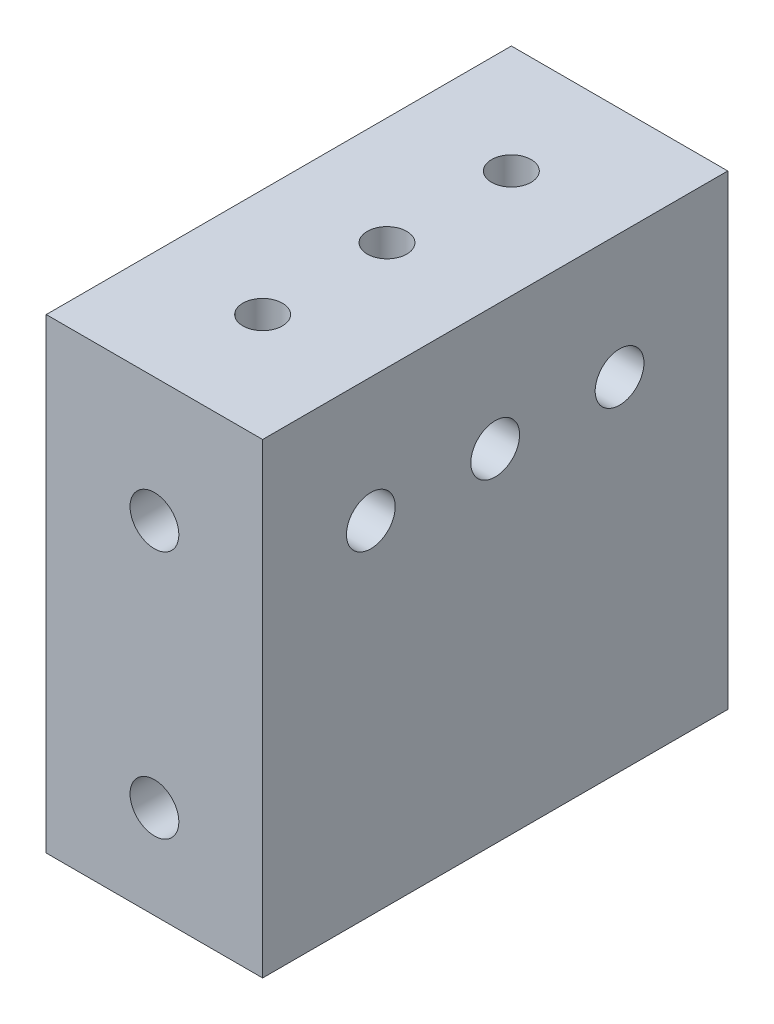
SolidWorks part; units mm, degrees
other "Markup1"
sketch "Sketch3" plane through (12.6365, 38.1, -23.749) normal (0.9027, 0.4189, -0.0984) x (-0.0151, -0.1977, -0.9801)
other "Markup2"
sketch "Sketch4" plane through (12.6365, 38.1, -23.749) normal (0.9027, 0.4189, -0.0984) x (-0.0151, -0.1977, -0.9801)
ref_plane "Front Plane" through (0, 0, 0) normal (0, 0, 1) x (1, 0, 0)
ref_plane "Top Plane" through (0, 0, 0) normal (0, 1, 0) x (1, 0, 0)
ref_plane "Right Plane" through (0, 0, 0) normal (1, 0, 0) x (0, 0, -1)
sketch "Sketch1" plane through (0, 0, 0) normal (0, 1, 0) x (1, 0, 0)
  line L0 (-12.6365, 25.3365) -> (12.6365, 25.3365)
  line L1 (-11.049, -23.749) -> (11.049, -23.749)
  line L2 (-11.049, -23.749) -> (-11.049, 23.749)
  line L3 (-11.049, 23.749) -> (11.049, 23.749)
  line L4 (11.049, -23.749) -> (11.049, 23.749)
  line L5 (-11.049, -23.749) -> (11.049, 23.749) construction
  line L6 (-11.049, 23.749) -> (11.049, -23.749) construction
  line L7 (12.6365, -25.3365) -> (12.6365, 25.3365)
  line L8 (-12.6365, -25.3365) -> (12.6365, -25.3365)
  line L9 (-12.6365, -25.3365) -> (-12.6365, 25.3365)
  point P0 (0, 0)
  dimension "D1" = 22.098
  dimension "D2" = 47.498
  dimension "D3" = 1.5875
extrude "Boss-Extrude1" add sketch "Sketch1" along normal mid plane 47.625 contours L1 L4 L3 L2 region at (0, 0, 0)
sketch "Sketch2" plane through (11.049, 0, 0) normal (1, 0, 0) x (0, 0, -1)
  line L0 (-23.749, 23.8125) -> (23.749, 23.8125) construction
  line L4 (-25.4, -23.8125) -> (25.4, -23.8125) construction
  line L5 (-25.4, -23.8125) -> (-25.4, 23.8125) construction
  line L6 (-25.4, 23.8125) -> (25.4, 23.8125) construction
  line L7 (25.4, -23.8125) -> (25.4, 23.8125) construction
  line L8 (-25.4, -23.8125) -> (25.4, 23.8125) construction
  line L9 (-25.4, 23.8125) -> (25.4, -23.8125) construction
  circle A0 centre (-12.7, 11.1125) radius 2.4892
  circle A1 centre (0, 11.1125) radius 2.4892
  circle A2 centre (12.7, 11.1125) radius 2.4892
  point P6 (0, 0)
  point P11 (0, 0)
  dimension "D1" = 4.9784
  dimension "D2" = 50.8
  dimension "D4" = 25.4
  dimension "D5" = 12.7
  dimension "D6" = 38.1
  dimension "D7" = 12.7
  dimension "D8" = 12.7
  dimension "D9" = 12.7
extrude "Cut-Extrude1" cut sketch "Sketch2" against normal blind 6.35
sketch "Sketch5" plane through (0, 0, -23.749) normal (0, 0, -1) x (-1, 0, 0)
  line L0 (11.049, 23.8125) -> (-11.049, 23.8125) construction
  line L1 (-12.7, -23.8125) -> (12.7, -23.8125) construction
  line L2 (-12.7, -23.8125) -> (-12.7, 23.8125) construction
  line L3 (-12.7, 23.8125) -> (12.7, 23.8125) construction
  line L4 (12.7, -23.8125) -> (12.7, 23.8125) construction
  line L5 (-12.7, -23.8125) -> (12.7, 23.8125) construction
  line L6 (-12.7, 23.8125) -> (12.7, -23.8125) construction
  circle A0 centre (0, 11.1125) radius 2.4892
  circle A2 centre (0, -14.2875) radius 2.4892
  point P0 (0, 0)
  dimension "D5" = 38.1
  dimension "D7" = 4.9784
  dimension "D8" = 4.9784
  dimension "D1" = 25.4
  dimension "D3" = 12.7
  dimension "D4" = 12.7
  dimension "D6" = 12.7
extrude "Cut-Extrude2" cut sketch "Sketch5" against normal through all
sketch "Sketch6" plane through (0, 23.8125, 0) normal (0, 1, 0) x (1, 0, 0)
  line L1 (11.049, -23.749) -> (11.049, 23.749) construction
  circle A0 centre (0, 0) radius 2.0193
  circle A1 centre (0, 12.7) radius 2.0193
  circle A2 centre (0, -12.7) radius 2.0193
  point P6 (0, 0)
  point P8 (0, 0)
  dimension "D3" = 4.0386
  dimension "D1" = 12.7
  dimension "D2" = 12.7
  dimension "D4" = 11.049
  dimension "D5" = 11.049
extrude "Cut-Extrude3" cut sketch "Sketch6" against normal blind 6.35
